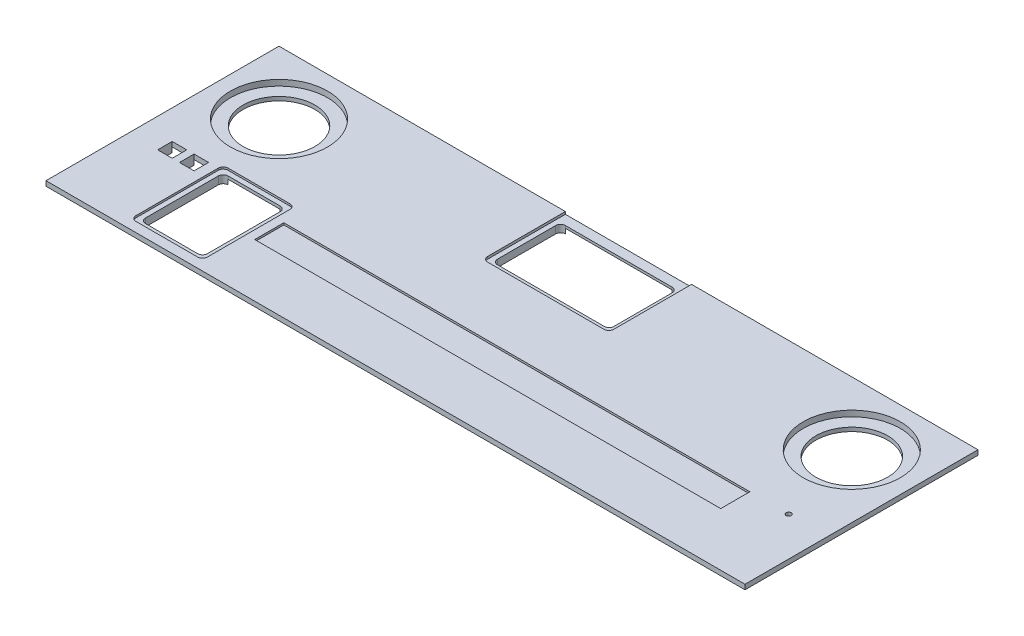
SolidWorks part; units mm, degrees
ref_plane "Front Plane" through (0, 0, 0) normal (0, 0, 1) x (1, 0, 0)
ref_plane "Top Plane" through (0, 0, 0) normal (0, 1, 0) x (1, 0, 0)
ref_plane "Right Plane" through (0, 0, 0) normal (1, 0, 0) x (0, 0, -1)
sketch "Sketch1" plane through (0, 0, 0) normal (0, 1, 0) x (1, 0, 0)
  line L1 (0, 0) -> (914.4, 0)
  line L2 (0, 0) -> (0, 304.8)
  line L3 (0, 304.8) -> (914.4, 304.8)
  line L4 (914.4, 0) -> (914.4, 304.8)
  dimension "D1" = 914.4
  dimension "D2" = 304.8
extrude "Boss-Extrude1" add sketch "Sketch1" along normal blind 12.7
sketch "Sketch3" plane through (0, 12.7, 0) normal (0, 1, 0) x (1, 0, 0)
  line L0 (933.9863, 107.95) -> (-7.7411, 107.95) construction
  line L1 (914.4, 0) -> (914.4, 304.8) construction
  line L2 (0, 304.8) -> (0, 0) construction
  line L3 (457.2, 304.8) -> (457.2, 0) construction
  line L4 (914.4, 304.8) -> (0, 304.8) construction
  line L5 (0, 0) -> (914.4, 0) construction
  line L6 (863.6, 304.8) -> (863.6, 0) construction
  line L8 (812.8, 96.2431) -> (812.8, 19.5383) construction
  line L9 (203.2, 151.0641) -> (203.2, 89.7006) construction
  line L10 (104.775, 133.35) -> (185.7375, 133.35)
  line L11 (203.2, 107.95) -> (812.8, 107.95)
  line L12 (203.2, 107.95) -> (203.2, 69.85)
  line L13 (203.2, 69.85) -> (812.8, 69.85)
  line L14 (812.8, 107.95) -> (812.8, 69.85)
  line L15 (38.1, 127) -> (57.15, 127)
  line L16 (38.1, 127) -> (38.1, 107.95)
  line L17 (38.1, 107.95) -> (57.15, 107.95)
  line L18 (57.15, 127) -> (57.15, 107.95)
  line L19 (66.675, 127) -> (85.725, 127)
  line L20 (66.675, 127) -> (66.675, 107.95)
  line L21 (66.675, 107.95) -> (85.725, 107.95)
  line L22 (85.725, 127) -> (85.725, 107.95)
  line L23 (98.425, 127) -> (98.425, 19.05)
  line L24 (381, 304.8) -> (533.4, 304.8) construction
  line L25 (381, 304.8) -> (381, 203.2) construction
  line L26 (381, 203.2) -> (533.4, 203.2) construction
  line L27 (533.4, 304.8) -> (533.4, 203.2) construction
  line L28 (152.4, 130.2491) -> (152.4, 0) construction
  line L29 (104.775, 12.7) -> (185.7375, 12.7)
  line L30 (192.0875, 127) -> (192.0875, 19.05)
  line L31 (169.2288, 116.8772) -> (169.2288, 116.6664)
  circle A0 centre (863.6, 107.95) radius 19.05
  circle A1 centre (152.4, 107.95) radius 19.05
  arc A2 (98.425, 19.05) -> (104.775, 12.7) centre (104.775, 19.05) ccw
  arc A3 (185.7375, 12.7) -> (192.0875, 19.05) centre (185.7375, 19.05) ccw
  arc A4 (185.7375, 133.35) -> (192.0875, 127) centre (185.7375, 127) cw
  arc A5 (104.775, 133.35) -> (98.425, 127) centre (104.775, 127) ccw
  circle A6 centre (82.55, 222.25) radius 63.5 construction
  circle A7 centre (831.85, 222.25) radius 63.5 construction
  circle A8 centre (111.125, 31.75) radius 6.35
  circle A9 centre (111.125, 63.5) radius 6.35
  circle A10 centre (142.875, 31.75) radius 6.35
  circle A11 centre (174.625, 31.75) radius 6.35
  point P54 (457.2, 203.2)
  point P61 (192.0875, 133.35)
  point P64 (98.425, 133.35)
  dimension "D6" = 12.7
  dimension "D7" = 38.1
  dimension "D16" = 6.35
  dimension "D18" = 127
  dimension "D19" = 107.95
  dimension "D22" = 127
  dimension "D28" = 38.1
  dimension "D29" = 12.7
  dimension "D30" = 12.7
  dimension "D31" = 12.7
  dimension "D32" = 12.7
  dimension "D1" = 50.8
  dimension "D2" = 50.8
  dimension "D3" = 609.6
  dimension "D4" = 93.6625
  dimension "D5" = 38.1
  dimension "D8" = 19.05
  dimension "D9" = 19.05
  dimension "D10" = 19.05
  dimension "D11" = 19.05
  dimension "D12" = 38.1
  dimension "D13" = 9.525
  dimension "D14" = 6.35
  dimension "D15" = 12.7
  dimension "D20" = 82.55
  dimension "D21" = 82.55
  dimension "D23" = 82.55
  dimension "D24" = 82.55
  dimension "D25" = 101.6
  dimension "D26" = 152.4
  dimension "D27" = 127
  dimension "D17" = 152.4
  dimension "D33" = 19.05
  dimension "D34" = 76.2
  dimension "D35" = 19.05
  dimension "D36" = 44.45
  dimension "D37" = 19.05
  dimension "D38" = 12.7
  dimension "D39" = 12.7
  dimension "D40" = 50.8
sketch "Sketch4" plane through (0, 12.7, 0) normal (0, 1, 0) x (1, 0, 0)
  line L0 (0, 304.8) -> (0, 127)
  line L1 (12.7, 292.1) -> (317.5, 292.1)
  line L2 (12.7, 292.1) -> (12.7, 139.7)
  line L3 (12.7, 139.7) -> (311.15, 139.7)
  line L4 (317.5, 292.1) -> (317.5, 146.05)
  line L5 (596.9, 292.1) -> (901.7, 292.1)
  line L6 (596.9, 292.1) -> (596.9, 146.05)
  line L7 (603.25, 139.7) -> (901.7, 139.7)
  line L8 (901.7, 292.1) -> (901.7, 139.7)
  line L9 (0, 127) -> (323.85, 127)
  line L10 (330.2, 304.8) -> (330.2, 133.35)
  line L11 (0, 304.8) -> (330.2, 304.8)
  line L12 (584.2, 304.8) -> (584.2, 133.35)
  line L13 (590.55, 127) -> (914.4, 127)
  line L14 (914.4, 304.8) -> (914.4, 127)
  line L15 (584.2, 304.8) -> (914.4, 304.8)
  line L16 (0, 304.8) -> (0, 0) construction
  line L17 (914.4, 304.8) -> (0, 304.8) construction
  line L18 (914.4, 0) -> (914.4, 304.8) construction
  line L19 (0, 127) -> (330.2, 127) construction
  line L20 (330.2, 304.8) -> (330.2, 127) construction
  line L21 (12.7, 139.7) -> (317.5, 139.7) construction
  line L22 (317.5, 292.1) -> (317.5, 139.7) construction
  line L23 (584.2, 304.8) -> (584.2, 127) construction
  line L24 (584.2, 127) -> (914.4, 127) construction
  line L25 (596.9, 292.1) -> (596.9, 139.7) construction
  line L26 (596.9, 139.7) -> (901.7, 139.7) construction
  arc A0 (323.85, 127) -> (330.2, 133.35) centre (323.85, 133.35) ccw
  arc A1 (311.15, 139.7) -> (317.5, 146.05) centre (311.15, 146.05) ccw
  arc A2 (584.2, 133.35) -> (590.55, 127) centre (590.55, 133.35) ccw
  arc A3 (596.9, 146.05) -> (603.25, 139.7) centre (603.25, 146.05) ccw
  point P34 (596.9, 139.7)
  dimension "D6" = 6.35
  dimension "D1" = 304.8
  dimension "D2" = 152.4
  dimension "D3" = 304.8
  dimension "D4" = 152.4
  dimension "D5" = 12.7
sketch "Sketch5" plane through (0, 12.7, 0) normal (0, 1, 0) x (1, 0, 0)
  line L0 (203.2, 107.95) -> (203.2, 69.85) construction
  line L1 (203.2, 107.95) -> (203.2, 69.85)
  line L2 (203.2, 69.85) -> (812.8, 69.85) construction
  line L3 (203.2, 69.85) -> (812.8, 69.85)
  line L12 (812.8, 107.95) -> (812.8, 69.85) construction
  line L13 (203.2, 107.95) -> (812.8, 107.95) construction
  line L14 (812.8, 107.95) -> (812.8, 69.85)
  line L15 (203.2, 107.95) -> (812.8, 107.95)
extrude "Cut-Extrude3" cut sketch "Sketch5" against normal blind 2.54
sketch "Sketch6" plane through (0, 12.7, 0) normal (0, 1, 0) x (1, 0, 0)
  circle A0 centre (82.55, 222.25) radius 46.99
  circle A1 centre (831.85, 222.25) radius 46.99
  dimension "D1" = 93.98
  dimension "D2" = 93.98
extrude "Cut-Extrude4" cut sketch "Sketch6" against normal through all
sketch "Sketch7" plane through (0, 12.7, 0) normal (0, 1, 0) x (1, 0, 0)
  circle A0 centre (82.55, 222.25) radius 63.5 construction
  circle A1 centre (82.55, 222.25) radius 63.5
  circle A2 centre (831.85, 222.25) radius 63.5 construction
  circle A3 centre (831.85, 222.25) radius 63.5
extrude "Cut-Extrude5" cut sketch "Sketch7" against normal blind 7.62
sketch "Sketch8" plane through (0, 12.7, 0) normal (0, 1, 0) x (1, 0, 0)
  line L0 (381, 304.8) -> (381, 203.2) construction
  line L1 (381, 203.2) -> (533.4, 203.2) construction
  line L2 (533.4, 304.8) -> (533.4, 203.2) construction
  line L4 (381, 285.75) -> (381, 209.55)
  line L5 (387.35, 203.2) -> (527.05, 203.2)
  line L6 (533.4, 285.75) -> (533.4, 209.55)
  line L7 (527.05, 292.1) -> (387.35, 292.1)
  line L8 (914.4, 304.8) -> (0, 304.8) construction
  arc A0 (527.05, 292.1) -> (533.4, 285.75) centre (527.05, 285.75) cw
  arc A1 (527.05, 203.2) -> (533.4, 209.55) centre (527.05, 209.55) ccw
  arc A2 (381, 209.55) -> (387.35, 203.2) centre (387.35, 209.55) ccw
  arc A3 (387.35, 292.1) -> (381, 285.75) centre (387.35, 285.75) ccw
  dimension "D2" = 6.35
  dimension "D1" = 12.7
extrude "Cut-Extrude6" cut sketch "Sketch8" against normal through all
sketch "Sketch9" plane through (0, 12.7, 0) normal (0, 1, 0) x (1, 0, 0)
  line L0 (914.4, 304.8) -> (0, 304.8) construction
  line L1 (539.75, 304.8) -> (374.65, 304.8)
  line L2 (539.75, 304.8) -> (539.75, 202.946)
  line L3 (533.4, 196.596) -> (381, 196.596)
  line L4 (374.65, 304.8) -> (374.65, 202.946)
  line L5 (381, 304.8) -> (381, 203.2) construction
  line L6 (381, 203.2) -> (533.4, 203.2) construction
  line L7 (457.2, 304.8) -> (457.2, 0) construction
  arc A0 (539.75, 202.946) -> (533.4, 196.596) centre (533.4, 202.946) cw
  arc A1 (381, 196.596) -> (374.65, 202.946) centre (381, 202.946) cw
  point P10 (457.2, 196.596)
  dimension "D3" = 6.35
  dimension "D1" = 6.35
  dimension "D2" = 6.604
  dimension "D4" = 165.1
  dimension "D5" = 108.204
extrude "Cut-Extrude7" cut sketch "Sketch9" against normal blind 3.175
sketch "Sketch13" plane through (0, 12.7, 0) normal (0, 1, 0) x (1, 0, 0)
  line L0 (57.15, 127) -> (57.15, 107.95) construction
  line L1 (38.1, 107.95) -> (57.15, 107.95)
  line L2 (38.1, 107.95) -> (38.1, 127)
  line L3 (38.1, 127) -> (57.15, 127)
  line L4 (57.15, 107.95) -> (57.15, 127)
  line L5 (85.725, 127) -> (85.725, 107.95) construction
  line L6 (66.675, 107.95) -> (85.725, 107.95)
  line L7 (66.675, 107.95) -> (66.675, 127)
  line L8 (66.675, 127) -> (85.725, 127)
  line L9 (85.725, 107.95) -> (85.725, 127)
  dimension "D1" = 19.05
  dimension "D2" = 19.05
  dimension "D3" = 19.05
extrude "Cut-Extrude11" cut sketch "Sketch13" against normal through all
sketch "Sketch14" plane through (0, 12.7, 0) normal (0, 1, 0) x (1, 0, 0)
  line L0 (38.1, 127) -> (38.1, 107.95) construction
  line L1 (38.1, 127) -> (57.15, 127) construction
  line L2 (57.15, 127) -> (57.15, 107.95) construction
  line L3 (38.1, 107.95) -> (57.15, 107.95) construction
  line L4 (66.675, 127) -> (66.675, 107.95) construction
  line L5 (66.675, 127) -> (85.725, 127) construction
  line L6 (85.725, 127) -> (85.725, 107.95) construction
  line L7 (66.675, 107.95) -> (85.725, 107.95) construction
  line L8 (38.1, 127) -> (38.1, 107.95)
  line L9 (38.1, 127) -> (57.15, 127)
  line L10 (57.15, 127) -> (57.15, 107.95)
  line L11 (38.1, 107.95) -> (57.15, 107.95)
  line L12 (66.675, 127) -> (66.675, 107.95)
  line L13 (66.675, 127) -> (85.725, 127)
  line L14 (85.725, 127) -> (85.725, 107.95)
  line L15 (66.675, 107.95) -> (85.725, 107.95)
extrude "Cut-Extrude12" [suppressed] cut sketch "Sketch14" against normal blind 5.08
sketch "Sketch21" plane through (0, 12.7, 0) normal (0, 1, 0) x (1, 0, 0)
  circle A0 centre (152.4, 107.95) radius 15.875
  dimension "D1" = 31.75
extrude "Cut-Extrude17" [suppressed] cut sketch "Sketch21" against normal through all
sketch "Sketch22" [suppressed] plane through (0, 12.7, 0) normal (0, 1, 0) x (1, 0, 0)
  circle A0 centre (152.4, 107.95) radius 22.225
  circle A1 centre (152.4, 107.95) radius 15.875 construction
  dimension "D1" = 6.35
extrude "Cut-Extrude18" [suppressed] cut sketch "Sketch22" against normal blind 2.54
sketch "Sketch24" plane through (0, 12.7, 0) normal (0, 1, 0) x (1, 0, 0)
  line L0 (104.775, 133.35) -> (185.7375, 133.35) construction
  line L1 (192.0875, 127) -> (192.0875, 19.05) construction
  line L2 (104.775, 12.7) -> (185.7375, 12.7) construction
  line L3 (98.425, 127) -> (98.425, 19.05) construction
  line L4 (104.775, 133.35) -> (185.7375, 133.35) construction
  line L5 (192.0875, 127) -> (192.0875, 19.05) construction
  line L6 (104.775, 12.7) -> (185.7375, 12.7) construction
  line L7 (98.425, 127) -> (98.425, 19.05) construction
  line L8 (111.125, 127) -> (179.3875, 127)
  line L9 (185.7375, 120.65) -> (185.7375, 25.4)
  line L10 (111.125, 19.05) -> (179.3875, 19.05)
  line L11 (104.775, 120.65) -> (104.775, 25.4)
  line L12 (104.775, 19.05) -> (185.7375, 19.05) construction
  line L13 (104.775, 127) -> (104.775, 19.05) construction
  line L14 (185.7375, 127) -> (185.7375, 19.05) construction
  line L15 (104.775, 127) -> (185.7375, 127) construction
  arc A0 (192.0875, 127) -> (185.7375, 133.35) centre (185.7375, 127) ccw construction
  arc A1 (185.7375, 12.7) -> (192.0875, 19.05) centre (185.7375, 19.05) ccw construction
  arc A2 (98.425, 19.05) -> (104.775, 12.7) centre (104.775, 19.05) ccw construction
  arc A3 (104.775, 133.35) -> (98.425, 127) centre (104.775, 127) ccw construction
  arc A4 (192.0875, 127) -> (185.7375, 133.35) centre (185.7375, 127) ccw construction
  arc A5 (185.7375, 12.7) -> (192.0875, 19.05) centre (185.7375, 19.05) ccw construction
  arc A6 (98.425, 19.05) -> (104.775, 12.7) centre (104.775, 19.05) ccw construction
  arc A7 (104.775, 133.35) -> (98.425, 127) centre (104.775, 127) ccw construction
  arc A8 (104.775, 120.65) -> (111.125, 127) centre (111.125, 120.65) cw
  arc A9 (179.3875, 127) -> (185.7375, 120.65) centre (179.3875, 120.65) cw
  arc A10 (179.3875, 19.05) -> (185.7375, 25.4) centre (179.3875, 25.4) ccw
  arc A12 (111.125, 19.05) -> (104.775, 25.4) centre (111.125, 25.4) cw
  arc A13 (104.775, 19.05) -> (104.775, 19.05) centre (104.775, 19.05) ccw construction
  arc A14 (185.7375, 19.05) -> (185.7375, 19.05) centre (185.7375, 19.05) ccw construction
  arc A15 (185.7375, 127) -> (185.7375, 127) centre (185.7375, 127) ccw construction
  arc A16 (104.775, 127) -> (104.775, 127) centre (104.775, 127) ccw construction
  dimension "D2" = 6.35
  dimension "D1" = 6.35
extrude "Cut-Extrude19" cut sketch "Sketch24" against normal through all
sketch "Sketch25" plane through (0, 12.7, 0) normal (0, 1, 0) x (1, 0, 0)
  line L0 (104.775, 133.35) -> (185.7375, 133.35) construction
  line L1 (192.0875, 127) -> (192.0875, 19.05) construction
  line L2 (104.775, 12.7) -> (185.7375, 12.7) construction
  line L3 (98.425, 127) -> (98.425, 19.05) construction
  line L4 (104.775, 133.35) -> (185.7375, 133.35)
  line L5 (192.0875, 127) -> (192.0875, 19.05)
  line L6 (104.775, 12.7) -> (185.7375, 12.7)
  line L7 (98.425, 127) -> (98.425, 19.05)
  arc A0 (192.0875, 127) -> (185.7375, 133.35) centre (185.7375, 127) ccw construction
  arc A1 (185.7375, 12.7) -> (192.0875, 19.05) centre (185.7375, 19.05) ccw construction
  arc A2 (98.425, 19.05) -> (104.775, 12.7) centre (104.775, 19.05) ccw construction
  arc A3 (104.775, 133.35) -> (98.425, 127) centre (104.775, 127) ccw construction
  arc A4 (192.0875, 127) -> (185.7375, 133.35) centre (185.7375, 127) ccw
  arc A5 (185.7375, 12.7) -> (192.0875, 19.05) centre (185.7375, 19.05) ccw
  arc A6 (98.425, 19.05) -> (104.775, 12.7) centre (104.775, 19.05) ccw
  arc A7 (104.775, 133.35) -> (98.425, 127) centre (104.775, 127) ccw
extrude "Cut-Extrude20" cut sketch "Sketch25" against normal blind 2.54
sketch "Sketch26" plane through (0, 12.7, 0) normal (0, 1, 0) x (1, 0, 0)
  circle A0 centre (863.6, 107.95) radius 3.302
  dimension "D1" = 6.604
extrude "Cut-Extrude21" cut sketch "Sketch26" against normal through all
sketch "Sketch19" plane through (0, 0, 0) normal (0, -1, 0) x (1, 0, 0)
  line L0 (0, -127) -> (323.85, -127) construction
  line L1 (0, 0) -> (914.4, 0)
  line L2 (0, 0) -> (0, -304.8)
  line L3 (0, -304.8) -> (914.4, -304.8)
  line L4 (914.4, 0) -> (914.4, -304.8)
  line L5 (596.9, -292.1) -> (596.9, -146.05) construction
  line L6 (12.7, -139.7) -> (12.7, -292.1)
  line L7 (12.7, -292.1) -> (317.5, -292.1)
  line L8 (603.25, -139.7) -> (901.7, -139.7) construction
  line L9 (590.55, -127) -> (914.4, -127) construction
  line L10 (330.2, -304.8) -> (330.2, -133.35) construction
  line L11 (596.9, -292.1) -> (901.7, -292.1)
  line L12 (901.7, -139.7) -> (901.7, -292.1)
  line L13 (317.5, -292.1) -> (317.5, -146.05) construction
  line L14 (12.7, -127) -> (12.7, -12.7)
  line L15 (12.7, -12.7) -> (901.7, -12.7)
  line L16 (901.7, -127) -> (901.7, -12.7)
  line L17 (584.2, -304.8) -> (584.2, -133.35) construction
  line L18 (12.7, -139.7) -> (311.15, -139.7) construction
  line L19 (596.9, -292.1) -> (596.9, -146.05)
  line L20 (330.2, -292.1) -> (584.2, -292.1)
  line L21 (603.25, -139.7) -> (901.7, -139.7)
  line L22 (590.55, -127) -> (901.7, -127)
  line L23 (584.2, -292.1) -> (584.2, -133.35)
  line L24 (330.2, -292.1) -> (330.2, -133.35)
  line L25 (317.5, -292.1) -> (317.5, -146.05)
  line L26 (12.7, -127) -> (323.85, -127)
  line L27 (12.7, -139.7) -> (311.15, -139.7)
  arc A0 (603.25, -139.7) -> (596.9, -146.05) centre (603.25, -146.05) ccw construction
  arc A1 (590.55, -127) -> (584.2, -133.35) centre (590.55, -133.35) ccw construction
  arc A2 (317.5, -146.05) -> (311.15, -139.7) centre (311.15, -146.05) ccw construction
  arc A3 (330.2, -133.35) -> (323.85, -127) centre (323.85, -133.35) ccw construction
  arc A4 (603.25, -139.7) -> (596.9, -146.05) centre (603.25, -146.05) ccw
  arc A5 (590.55, -127) -> (584.2, -133.35) centre (590.55, -133.35) ccw
  arc A6 (317.5, -146.05) -> (311.15, -139.7) centre (311.15, -146.05) ccw
  arc A7 (330.2, -133.35) -> (323.85, -127) centre (323.85, -133.35) ccw
  line M10 (85.725, -127) -> (66.675, -127)
  line M14 (57.15, -127) -> (38.1, -127)
  line M18 (527.05, -292.1) -> (387.35, -292.1)
  line M22 (0, 0) -> (0, -304.8)
  line M23 (0, -304.8) -> (914.4, -304.8)
  line M24 (914.4, -304.8) -> (914.4, 0)
  line M25 (914.4, 0) -> (0, 0)
  dimension "D1" = 12.7
extrude "Cut-Extrude16" cut sketch "Sketch19" against normal blind 6.35 contours L21 L12 L11 L7 L6 L20 L14 L15 L16 M25 M22 M23 M24 M18 M10 M14 region at (457.2, 0, -9.6386)
sketch "Sketch23" plane through (0, 0, 0) normal (0, -1, 0) x (1, 0, 0)
  line L0 (847.9254, -12.7) -> (933.5678, -12.7)
  line L1 (12.7, -12.7) -> (901.7, -12.7) construction
  line L2 (901.7, -50.534) -> (901.7, 49.3195)
  line L3 (901.7, -127) -> (901.7, -12.7) construction
  line L5 (901.7, -12.7) -> (914.4, -12.7)
  line L6 (901.7, -12.7) -> (901.7, 0)
  line L7 (901.7, 0) -> (914.4, 0)
  line L8 (914.4, -12.7) -> (914.4, 0)
  dimension "D1" = 12.7
  dimension "D2" = 12.7
sketch "Sketch27" plane through (0, 12.7, 0) normal (0, 1, 0) x (1, 0, 0)
  line L0 (104.775, 133.35) -> (185.7375, 133.35) construction
  line L1 (192.0875, 127) -> (192.0875, 19.05) construction
  line L2 (104.775, 12.7) -> (185.7375, 12.7) construction
  line L3 (98.425, 127) -> (98.425, 19.05) construction
  line L4 (104.775, 133.35) -> (185.7375, 133.35)
  line L5 (192.0875, 127) -> (192.0875, 19.05)
  line L6 (104.775, 12.7) -> (185.7375, 12.7)
  line L7 (98.425, 127) -> (98.425, 19.05)
  line L8 (111.125, 127) -> (179.3875, 127) construction
  line L9 (111.125, 127) -> (179.3875, 127) construction
  line L10 (104.775, 25.4) -> (104.775, 120.65) construction
  line L11 (179.3875, 19.05) -> (111.125, 19.05) construction
  line L12 (185.7375, 120.65) -> (185.7375, 25.4) construction
  line L13 (104.775, 25.4) -> (104.775, 120.65) construction
  line L14 (179.3875, 19.05) -> (111.125, 19.05) construction
  line L15 (185.7375, 120.65) -> (185.7375, 25.4) construction
  line L16 (136.525, 129.0783) -> (136.525, 101.3305) construction
  line L18 (94.0016, 107.95) -> (212.4361, 107.95) construction
  line L19 (933.9863, 107.95) -> (-7.7411, 107.95) construction
  line L20 (203.2, 107.95) -> (812.8, 107.95) construction
  line L21 (136.525, 107.95) -> (116.6064, 119.45) construction
  line L22 (136.525, 107.95) -> (136.525, 80.2047) construction
  line L23 (136.525, 107.95) -> (156.4436, 119.45) construction
  line L24 (136.525, 107.95) -> (123.5346, 115.45) construction
  line L25 (136.525, 107.95) -> (149.5154, 115.45) construction
  line L26 (86.9826, 34.29) -> (208.5237, 34.29) construction
  line L27 (81.96, 70.3217) -> (211.1661, 70.3217) construction
  arc A0 (192.0875, 127) -> (185.7375, 133.35) centre (185.7375, 127) ccw construction
  arc A1 (185.7375, 12.7) -> (192.0875, 19.05) centre (185.7375, 19.05) ccw construction
  arc A2 (98.425, 19.05) -> (104.775, 12.7) centre (104.775, 19.05) ccw construction
  arc A3 (104.775, 133.35) -> (98.425, 127) centre (104.775, 127) ccw construction
  arc A4 (192.0875, 127) -> (185.7375, 133.35) centre (185.7375, 127) ccw
  arc A5 (185.7375, 12.7) -> (192.0875, 19.05) centre (185.7375, 19.05) ccw
  arc A6 (98.425, 19.05) -> (104.775, 12.7) centre (104.775, 19.05) ccw
  arc A7 (104.775, 133.35) -> (98.425, 127) centre (104.775, 127) ccw
  arc A8 (111.125, 127) -> (104.775, 120.65) centre (111.125, 120.65) ccw construction
  arc A9 (104.775, 25.4) -> (111.125, 19.05) centre (111.125, 25.4) ccw construction
  arc A10 (179.3875, 19.05) -> (185.7375, 25.4) centre (179.3875, 25.4) ccw construction
  arc A11 (185.7375, 120.65) -> (179.3875, 127) centre (179.3875, 120.65) ccw construction
  arc A12 (111.125, 127) -> (104.775, 120.65) centre (111.125, 120.65) ccw construction
  arc A13 (104.775, 25.4) -> (111.125, 19.05) centre (111.125, 25.4) ccw construction
  arc A14 (179.3875, 19.05) -> (185.7375, 25.4) centre (179.3875, 25.4) ccw construction
  arc A15 (185.7375, 120.65) -> (179.3875, 127) centre (179.3875, 120.65) ccw construction
  circle A16 centre (136.525, 107.95) radius 10.1
  circle A17 centre (136.525, 107.95) radius 23 construction
  circle A18 centre (136.525, 107.95) radius 15 construction
  circle A19 centre (123.5346, 115.45) radius 1.75
  circle A20 centre (149.5154, 115.45) radius 1.75
  circle A21 centre (136.525, 92.95) radius 1.75
  circle A22 centre (120.015, 34.29) radius 8.255 construction
  circle A23 centre (158.115, 34.29) radius 8.255 construction
  circle A24 centre (170.4975, 70.3217) radius 8.255 construction
  circle A25 centre (132.3975, 70.3217) radius 8.255 construction
  circle A26 centre (120.015, 34.29) radius 4.445
  circle A27 centre (158.115, 34.29) radius 4.445
  circle A28 centre (170.4975, 70.3217) radius 4.445
  circle A29 centre (132.3975, 70.3217) radius 4.445
  point P44 (136.525, 107.95)
  dimension "D1" = 20.2
  dimension "D2" = 46
  dimension "D5" = 30
  dimension "D6" = 3.5
  dimension "D11" = 16.51
  dimension "D13" = 16.51
  dimension "D15" = 16.51
  dimension "D17" = 16.51
  dimension "D19" = 8.89
  dimension "D20" = 8.89
  dimension "D21" = 8.89
  dimension "D22" = 8.89
  dimension "D3" = 38.1
  dimension "D8" = 120
  dimension "D9" = 15.24
  dimension "D10" = 38.1
  dimension "D12" = 15.24
  dimension "D14" = 38.1
  dimension "D16" = 15.24
  dimension "D18" = 38.1
  dimension "D4" = 3
  dimension "D7" = 3
equation "\"D2@Sketch12\" = \"D1@Sketch12\""
equation "\"D3@Sketch12\" = \"D1@Sketch12\""
equation "\"D4@Sketch12\" = \"D1@Sketch12\""
equation "\"D3@Sketch13\" = \"D1@Sketch13\""
equation "\"D6@Sketch15\" = \"D4@Sketch15\" / 2"
equation "\"D9@Sketch3\"=\"D8@Sketch3\""
equation "\"D13@Sketch27\"=\"D11@Sketch27\""
equation "\"D15@Sketch27\"=\"D11@Sketch27\""
equation "\"D17@Sketch27\"=\"D11@Sketch27\""
equation "\"D20@Sketch27\"=\"D19@Sketch27\""
equation "\"D21@Sketch27\"=\"D19@Sketch27\""
equation "\"D22@Sketch27\"=\"D19@Sketch27\""
